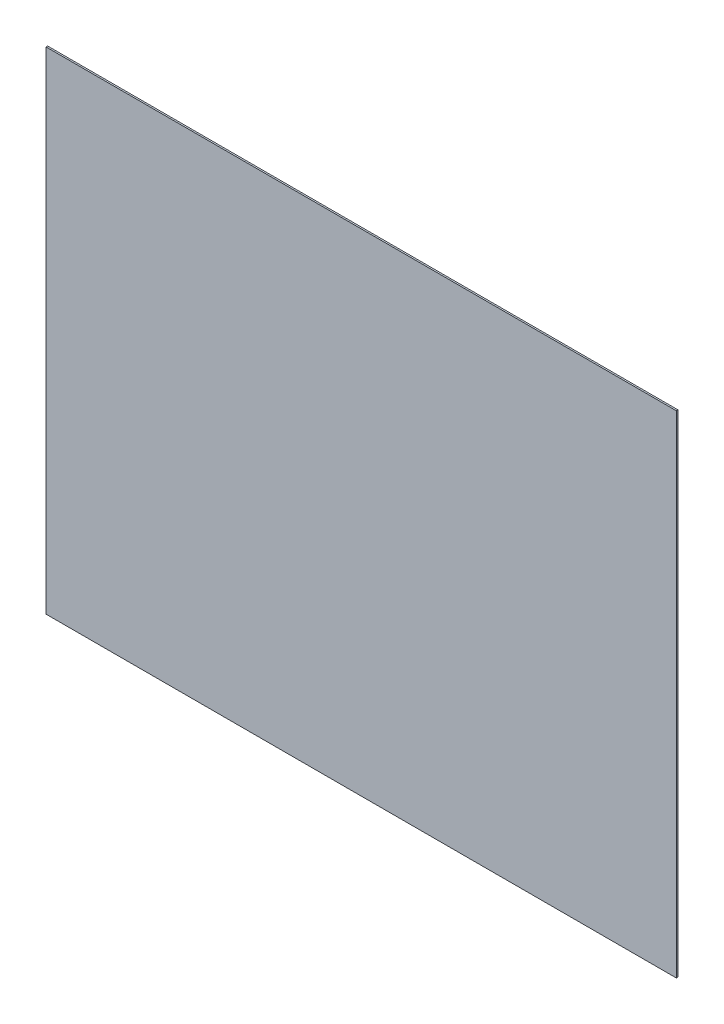
SolidWorks part; units mm, degrees
material "ABS"
ref_plane "X-Y Datum" through (0, 0, 0) normal (0, 0, 1) x (1, 0, 0)
ref_plane "X-Z Datum" through (0, 0, 0) normal (0, 1, 0) x (1, 0, 0)
ref_plane "Y-Z Datum" through (0, 0, 0) normal (1, 0, 0) x (0, 0, -1)
sketch "Sketch2" plane through (0, 0, 0) normal (0, 0, 1) x (1, 0, 0)
  line L8 (-157.564, 102.4228) -> (-157.5131, -381.8282)
  line L9 (-157.5131, -381.8282) -> (463.7455, -381.7629)
  line L10 (463.7455, -381.7629) -> (463.6946, 102.4881)
  line L11 (463.6946, 102.4881) -> (-157.564, 102.4228)
extrude "Boss-Extrude1" add sketch "Sketch2" along normal blind 1.5875
